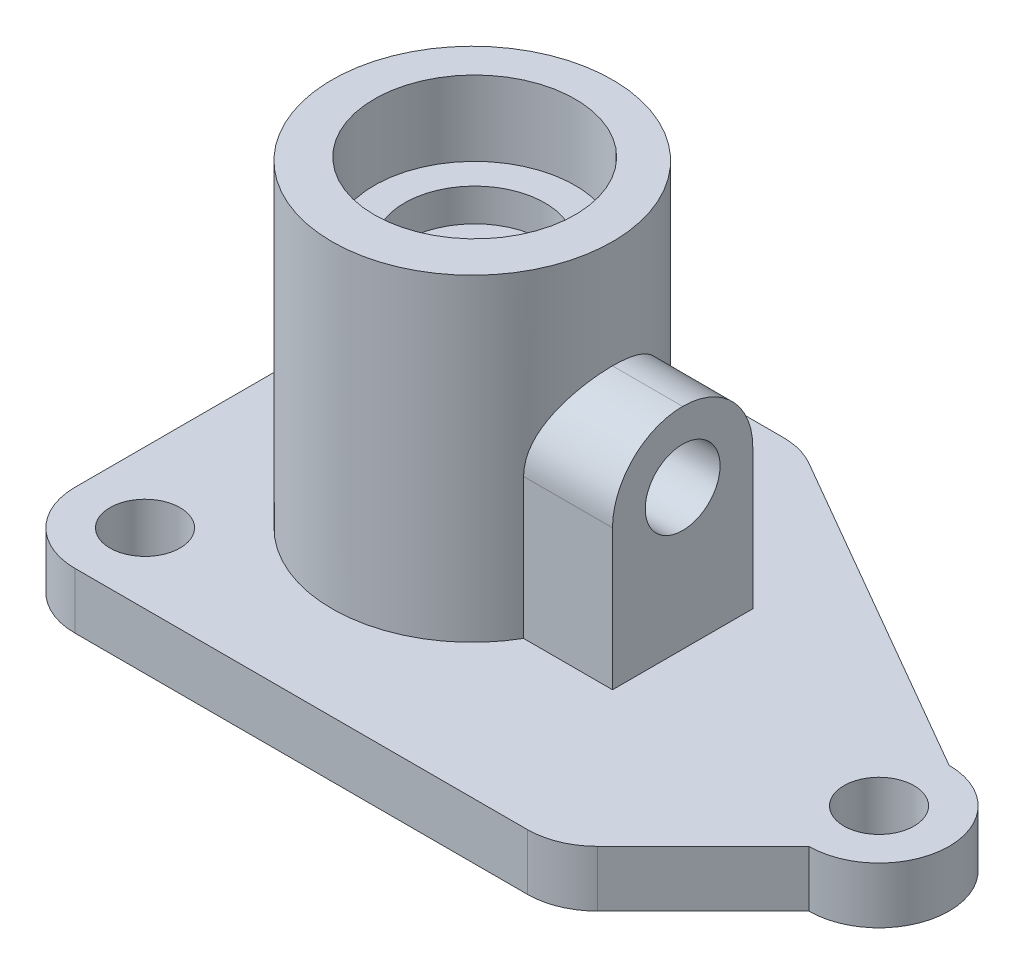
SolidWorks part; units mm, degrees
ref_plane "Front Plane" through (0, 0, 0) normal (0, 0, 1) x (1, 0, 0)
ref_plane "Top Plane" through (0, 0, 0) normal (0, 1, 0) x (1, 0, 0)
ref_plane "Right Plane" through (0, 0, 0) normal (1, 0, 0) x (0, 0, -1)
sketch "Sketch2" plane through (0, 0, 0) normal (0, 1, 0) x (1, 0, 0)
  line L0 (0, 15) -> (0, 85)
  line L1 (15, 100) -> (66.5026, 100)
  line L2 (74.0026, 97.9904) -> (145, 57)
  line L3 (15, 0) -> (111.7868, 0)
  line L4 (122.3934, 4.3934) -> (145, 27)
  arc A0 (15, 0) -> (0, 15) centre (15, 15) cw
  circle A1 centre (145, 42) radius 7.5
  arc A2 (145, 27) -> (145, 57) centre (145, 42) ccw
  arc A3 (122.3934, 4.3934) -> (111.7868, 0) centre (111.7868, 15) cw
  arc A4 (74.0026, 97.9904) -> (66.5026, 100) centre (66.5026, 85) ccw
  arc A5 (15, 100) -> (0, 85) centre (15, 85) ccw
  circle A9 centre (15, 85) radius 7.5
  circle A10 centre (15, 15) radius 7.5
  point P12 (0, 0)
  point P15 (118, 0)
  point P20 (0, 100)
  dimension "D1" = 7.5
  dimension "D2" = 30
  dimension "D3" = 145
  dimension "D6" = 30
  dimension "D7" = 15
  dimension "D8" = 15
  dimension "D9" = 15
  dimension "D10" = 15
  dimension "D11" = 15
  dimension "D12" = 15
  dimension "D4" = 135
  dimension "D5" = 100
  dimension "42" = 42
extrude "Boss-Extrude3" add sketch "Sketch2" along normal mid plane 12
sketch "Sketch4" plane through (0, 6, 0) normal (0, 1, 0) x (1, 0, 0)
  line L0 (15, 0) -> (111.7868, 0) construction
  line L3 (0, 85) -> (0, 15) construction
  circle A0 centre (50, 50) radius 30
  point P6 (0, 0)
  dimension "D3" = 60
  dimension "D4" = 50
  dimension "D5" = 50
extrude "Boss-Extrude6" add sketch "Sketch4" along normal blind 68
sketch "Sketch5" plane through (0, 74, 0) normal (0, 1, 0) x (1, 0, 0)
  circle A0 centre (49.5579, 50.9678) radius 15
  dimension "D1" = 30
extrude "Cut-Extrude1" cut sketch "Sketch5" against normal through all
sketch "Sketch6" plane through (0, 74, 0) normal (0, 1, 0) x (1, 0, 0)
  circle A0 centre (49.5579, 50.9678) radius 21.4722
  circle A1 centre (49.5579, 50.9678) radius 15 construction
extrude "Cut-Extrude3" cut sketch "Sketch6" against normal blind 16
sketch "Sketch8" plane through (0, 6, 0) normal (0, 1, 0) x (1, 0, 0)
  line L0 (50, 50) -> (122.2318, 50) construction
  line L1 (75.9808, 65) -> (95, 65)
  line L2 (95, 65) -> (95, 50)
  line L3 (95, 50) -> (95, 35)
  line L4 (95, 35) -> (75.9808, 35)
  circle A0 centre (50, 50) radius 30 construction
  circle A2 centre (50, 50) radius 30
  arc A3 (75.9808, 65) -> (75.9808, 35) centre (50, 50) ccw
  dimension "D1" = 15
  dimension "D2" = 30
  dimension "D3" = 45
  dimension "D4" = 0
extrude "Boss-Extrude7" add sketch "Sketch8" along normal blind 45
fillet "Fillet2" radius 15 2 edges at (85.4904, 51, -65) (85.4904, 51, -35)
sketch "Sketch9" plane through (95, 0, 0) normal (1, 0, 0) x (0, 0, -1)
  line L0 (57, 6) -> (27, 6) construction
  circle A0 centre (50, 36) radius 8
  arc A1 (65, 36) -> (50, 51) centre (50, 36) ccw construction
  dimension "D1" = 16
  dimension "D2" = 30
extrude "Cut-Extrude8" cut sketch "Sketch9" against normal mid plane 35
